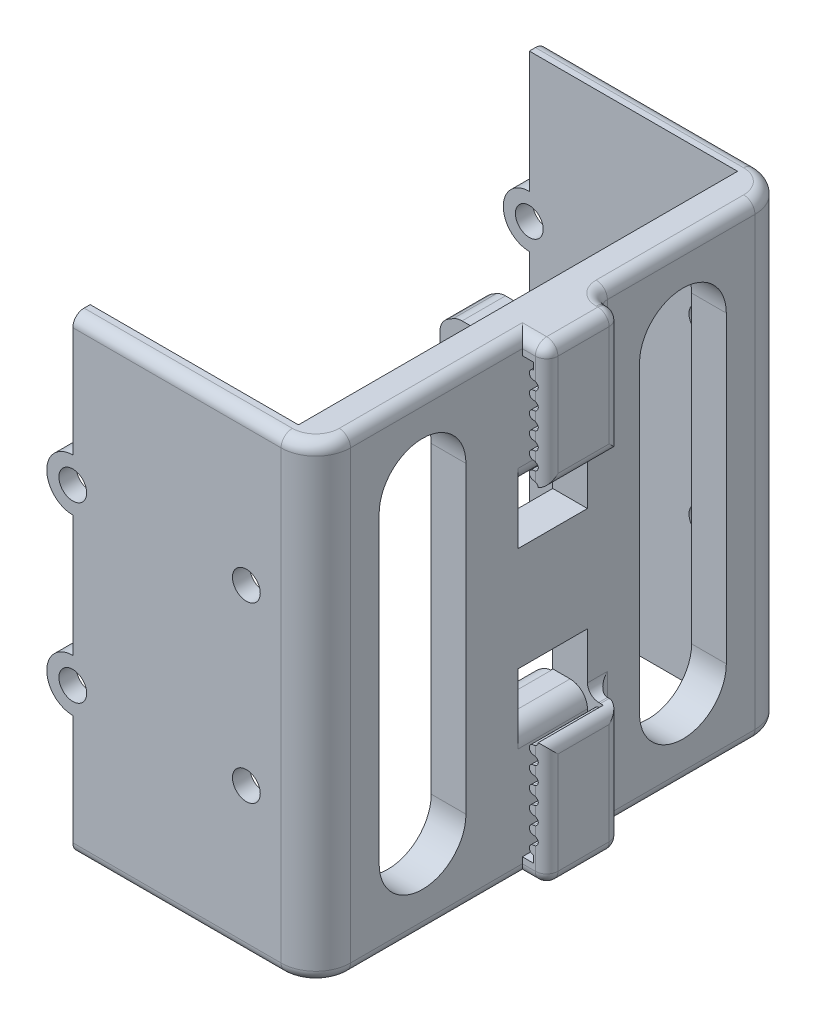
SolidWorks part; units mm, degrees
material "6063-T5"
ref_plane "Front Plane" through (0, 0, 0) normal (1, 0, 0) x (0, 1, 0)
ref_plane "Top Plane" through (0, 0, 0) normal (0, 0, 1) x (0, 1, 0)
ref_plane "Right Plane" through (0, 0, 0) normal (0, 1, 0) x (-1, 0, 0)
ref_plane "Plane1" through (0, 0, 25.3) normal (0, 0, 1) x (0, 1, 0)
sketch "Sketch1" plane through (0, 0, 25.3) normal (0, 0, 1) x (0, 1, 0)
  line L0 (-13, 12) -> (-27, 12)
  line L1 (-10, 12) -> (10, 12) construction
  line L2 (-10, 12) -> (-10, -8) construction
  line L3 (-10, -8) -> (10, -8) construction
  line L4 (10, 12) -> (10, -8) construction
  line L5 (-27, 12) -> (-27, -12)
  line L6 (-27, -12) -> (27, -12)
  line L7 (27, -12) -> (27, 12)
  line L8 (27, 12) -> (13, 12)
  line L9 (0, -12) -> (0, 0) construction
  line L10 (-7, 12) -> (7, 12)
  circle A0 centre (-10, 12) radius 1.6
  circle A1 centre (10, 12) radius 1.6
  circle A2 centre (10, -8) radius 1.6
  circle A3 centre (-10, -8) radius 1.6
  arc A4 (-7, 12) -> (-13, 12) centre (-10, 12) ccw
  arc A7 (13, 12) -> (7, 12) centre (10, 12) ccw
  circle A8 centre (-10, 12) radius 3 construction
  circle A9 centre (10, 12) radius 3 construction
  point P13 (0, -8)
  dimension "D1" = 3.2
  dimension "D3" = 6
  dimension "D5" = 12
  dimension "D2" = 20
  dimension "D4" = 54
  dimension "D6" = 12
extrude "Boss-Extrude1" add sketch "Sketch1" along normal blind 2
mirror "Mirror3" about plane through (0, 0, 0) normal (0, 0, 1) of bodies 155
sketch "Sketch2" plane through (12, 0, 0) normal (1, 0, 0) x (0, 1, 0)
  line L0 (-6, 0) -> (6, 0) construction
  line L1 (-27, 27.3) -> (27, 27.3)
  line L2 (-27, 27.3) -> (-27, -27.3)
  line L3 (-27, -27.3) -> (27, -27.3)
  line L4 (27, 27.3) -> (27, -27.3)
  line L9 (-12, 4) -> (-6, 4)
  line L10 (-12, 4) -> (-12, -4)
  line L11 (-12, -4) -> (-6, -4)
  line L12 (-6, 4) -> (-6, -4)
  line L13 (6, 4) -> (12, 4)
  line L14 (6, 4) -> (6, -4)
  line L15 (6, -4) -> (12, -4)
  line L16 (12, 4) -> (12, -4)
  point P4 (0, 0)
  point P18 (0, 0)
  dimension "D1" = 8
  dimension "D2" = 6
  dimension "D3" = 12
extrude "Boss-Extrude2" add sketch "Sketch2" along normal blind 4
sketch "Sketch3" plane through (0, 0, 0) normal (0, 0, 1) x (0, 1, 0)
  line L0 (0, 0) -> (0, -12) construction
  line L1 (0, -12) -> (-24, -12) construction
  line L2 (6, -12) -> (12, -12) construction
  line L3 (-24, -12) -> (-24, -7.5)
  line L4 (-24, -7.5) -> (-22.8, -5.5)
  line L5 (-22.8, -5.5) -> (-20, -5.5)
  line L6 (-20, -5.5) -> (-12, -11)
  line L7 (-12, -11) -> (-12, -12)
  line L8 (-12, -12) -> (-24, -12)
  line L9 (12, -12) -> (24, -12)
  line L10 (12, -11) -> (12, -12)
  line L11 (20, -5.5) -> (12, -11)
  line L12 (22.8, -5.5) -> (20, -5.5)
  line L13 (24, -7.5) -> (22.8, -5.5)
  line L14 (24, -12) -> (24, -7.5)
  dimension "D1" = 6.5
  dimension "D2" = 2
  dimension "D3" = 12
  dimension "D4" = 1.2
  dimension "D5" = 2.8
  dimension "D6" = 1
extrude "Boss-Extrude6" add sketch "Sketch3" along normal blind 2.5 and the other way blind 2.5
sketch "Sketch5" plane through (0, 0, -2.5) normal (0, 0, -1) x (1, 0, 0)
  line L0 (12, 12) -> (11, 12)
  line L1 (11, 12) -> (10.3125, 13)
  line L2 (11, 12) -> (5.5, 20) construction
  line L3 (10.3125, 13) -> (12, 13)
  line L4 (12, 13) -> (12, 12)
  line L5 (12, 24) -> (12, 12) construction
  line L6 (-55, 0) -> (55, 0) construction
  line L7 (12, -13) -> (12, -12)
  line L8 (10.3125, -13) -> (12, -13)
  line L9 (11, -12) -> (10.3125, -13)
  line L10 (12, -12) -> (11, -12)
  dimension "D1" = 1
extrude "Boss-Extrude7" add sketch "Sketch5" along normal up to surface and the other way up to surface up to face at (14, -9, -4) other way up to face at (14, -9, 4)
fillet "Fillet3" radius 4 2 edges at (16, 0, 27.3) (16, 0, -27.3)
fillet "Fillet1" radius 2 6 edges at (7.5, 24, 0) (5.5, 22.8, 0) (5.5, 20, 0) (5.5, -20, 0) (5.5, -22.8, 0) (7.5, -24, 0)
fillet "Fillet2" radius 2 4 edges at (11, -12, 0) (16, -12, 0) (16, 12, 0) (11, 12, 0)
fillet "Fillet4" radius 2 4 edges at (11.1562, 13, 4) (11.1562, 13, -4) (11.1562, -13, -4) (11.1562, -13, 4)
sketch "Sketch6" plane through (0, 0, 0) normal (0, 0, 1) x (0, 1, 0)
  line L0 (-27, -16) -> (-27, -18.8)
  line L1 (-27, -18.8) -> (-12.7, -18.8)
  line L4 (-25, -17.3) -> (-25, -16)
  line L5 (-25, -16) -> (-27, -16)
  line L6 (-25, -17.3) -> (-24.2, -17.3)
  line L7 (-24.2, -17.3) -> (-23.2, -17.3) construction
  line L8 (-22.2, -17.3) -> (-23.2, -17.3) construction
  line L9 (-23.7, -16.8) -> (-23.7, -16) construction
  line L10 (27, -16) -> (-27, -16) construction
  line L11 (-22.7, -17.8) -> (-22.7, -18.8) construction
  line L12 (-12.7, -17.8) -> (-12.7, -18.8)
  arc A0 (-24.2, -17.3) -> (-23.2, -17.3) centre (-23.7, -17.3) cw
  arc A1 (-23.2, -17.3) -> (-22.2, -17.3) centre (-22.7, -17.3) ccw
  arc A2 (-22.2, -17.3) -> (-21.2, -17.3) centre (-21.7, -17.3) cw
  arc A3 (-21.2, -17.3) -> (-20.2, -17.3) centre (-20.7, -17.3) ccw
  arc A4 (-20.2, -17.3) -> (-19.2, -17.3) centre (-19.7, -17.3) cw
  arc A5 (-19.2, -17.3) -> (-18.2, -17.3) centre (-18.7, -17.3) ccw
  arc A6 (-18.2, -17.3) -> (-17.2, -17.3) centre (-17.7, -17.3) cw
  arc A7 (-17.2, -17.3) -> (-16.2, -17.3) centre (-16.7, -17.3) ccw
  arc A8 (-16.2, -17.3) -> (-15.2, -17.3) centre (-15.7, -17.3) cw
  arc A9 (-15.2, -17.3) -> (-14.2, -17.3) centre (-14.7, -17.3) ccw
  arc A10 (-14.2, -17.3) -> (-13.2, -17.3) centre (-13.7, -17.3) cw
  arc A11 (-13.2, -17.3) -> (-12.7, -17.8) centre (-12.7, -17.3) ccw
  point P37 (-12.7208, -18.8)
  dimension "D1" = 1
  dimension "D2" = 2
  dimension "D3" = 0.8
  dimension "D4" = 0.8
  dimension "D5" = 6
  dimension "D6" = 1
extrude "Boss-Extrude8" add sketch "Sketch6" along normal blind 3.5 and the other way blind 4
sketch "Sketch7" plane through (0, 0, -4) normal (0, 0, -1) x (1, 0, 0)
  line L0 (16, 27) -> (16, -27) construction
  line L1 (18.8, 27) -> (16, 27)
  line L2 (18.8, 27) -> (18.8, 12.7)
  line L3 (18.8, 12.7) -> (16, 12.7)
  line L4 (16, 27) -> (16, 12.7)
  point P4 (18.8, 12.7)
extrude "Boss-Extrude9" add sketch "Sketch7" along normal blind 1
mirror "Mirror4" about plane through (0, 0, 0) normal (0, 1, 0) of "Boss-Extrude9", "Boss-Extrude8"
fillet "Fillet5" radius 1.3 32 edges at (0, -27, 27.3) (16, -27, 13.4) (16, 27, -14.15) (0, -27, -27.3) (14.8284, -27, -26.1284) (14.8284, -27, 26.1284) (0, 27, 27.3) (0, 27, -27.3) (14.8284, 27, -26.1284) (14.8284, 27, 26.1284) (17.8, -12.7, -0.25) (18.3, -12.7, 3.5) (18.8, -12.7, -0.75) (18.8, -27, -0.75) (17.4, -27, 3.5) (18.8, -19.85, 3.5) (16, -27, -14.15) (16, -12.7, -4.5) (18.8, -19.85, -5) (17.4, -27, -5) (16, -19.85, -5) (16, 27, 13.4) (17.8, 12.7, -0.25) (17.4, 27, 3.5) (18.8, 27, -0.75) (18.8, 19.85, 3.5) (18.8, 12.7, -0.75) (18.3, 12.7, 3.5) (18.8, 19.85, -5) (16, 19.85, -5) (16, 12.7, -4.5) (17.4, 27, -5)
sketch "Sketch8" plane through (16, 0, 0) normal (1, 0, 0) x (0, 1, 0)
  line L0 (-17.5, 15) -> (17.5, 15) construction
  line L1 (-17.5, 20) -> (17.5, 20)
  line L2 (-17.5, 10) -> (17.5, 10)
  line L3 (0, 15) -> (0, 0) construction
  line L4 (18.59, 0) -> (-18.59, 0) construction
  line L5 (-17.5, -15) -> (17.5, -15) construction
  line L6 (-17.5, -20) -> (17.5, -20)
  line L7 (-17.5, -10) -> (17.5, -10)
  arc A0 (-17.5, 20) -> (-17.5, 10) centre (-17.5, 15) ccw
  arc A1 (17.5, 10) -> (17.5, 20) centre (17.5, 15) ccw
  arc A2 (-17.5, -20) -> (-17.5, -10) centre (-17.5, -15) cw
  arc A3 (17.5, -10) -> (17.5, -20) centre (17.5, -15) cw
  point P2 (0, 15)
  point P14 (0, -15)
  dimension "D2" = 5
  dimension "D1" = 15
  dimension "D3" = 35
  dimension "D4" = 15
extrude "Cut-Extrude1" cut sketch "Sketch8" against normal up to surface (4 mm away) up to face at (12, 13.427, 0)
